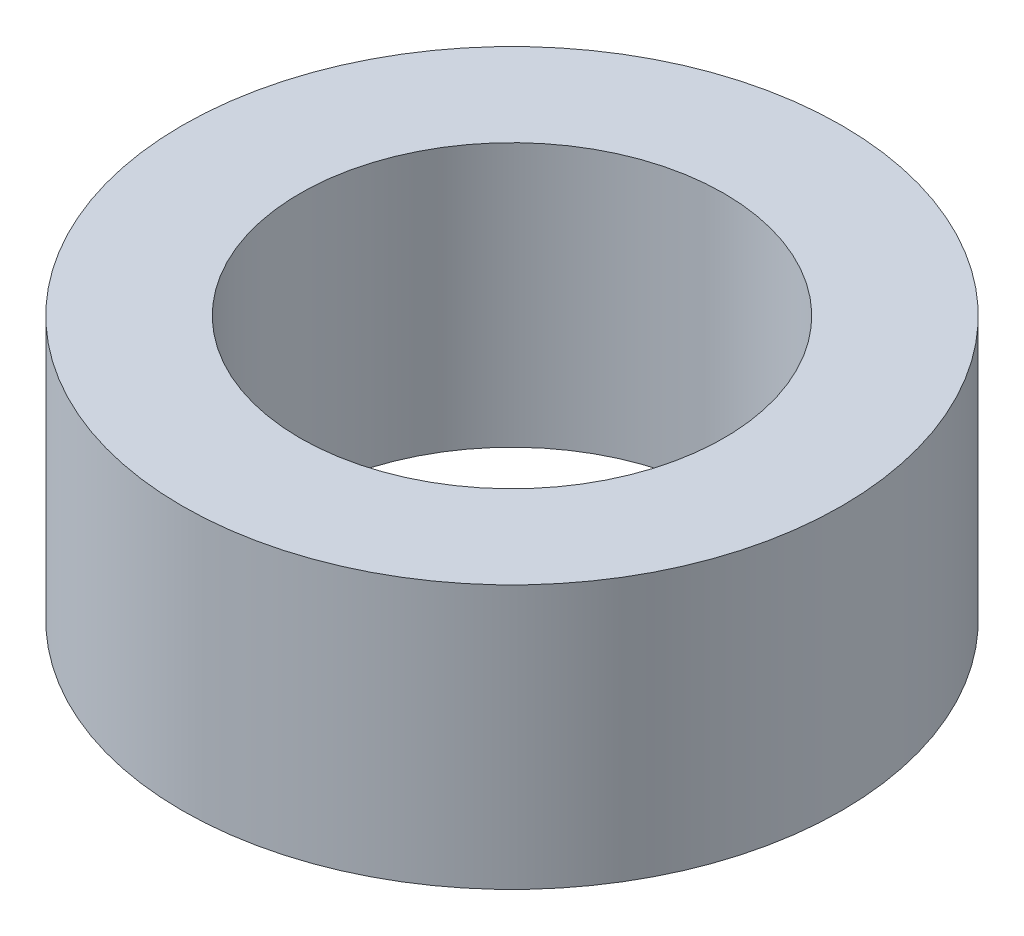
SolidWorks part; units mm, degrees
ref_plane "Front Plane" through (0, 0, 0) normal (0, 0, 1) x (1, 0, 0)
ref_plane "Top Plane" through (0, 0, 0) normal (0, 1, 0) x (1, 0, 0)
ref_plane "Right Plane" through (0, 0, 0) normal (1, 0, 0) x (0, 0, -1)
sketch "Sketch1" plane through (0, 0, 0) normal (0, 1, 0) x (1, 0, 0)
  circle A0 centre (0, 0) radius 35
  dimension "FLANGE_OD" = 70
extrude "Boss-Extrude1" add sketch "Sketch1" along normal blind 28
sketch "Sketch2" plane through (0, 0, 0) normal (0, 1, 0) x (1, 0, 0)
  circle A0 centre (0, 0) radius 22.5
  dimension "BORE_D" = 45
extrude "Cut-Extrude1" cut sketch "Sketch2" along normal through all
sketch "Sketch3" plane through (0, 28, 0) normal (0, 1, 0) x (1, 0, 0)
  circle A0 centre (0, 0) radius 13.3964 construction
  circle A1 centre (-13.3964, 0) radius 2.0669
  dimension "BOLT_D" = 4.1339
  dimension "BOLT_PCD" = 26.7928
extrude "Cut-Extrude2" cut sketch "Sketch3" against normal blind 21.217 rebuild error yes
pattern_circular "CirPattern1" count 6 over 360 rebuild error yes
